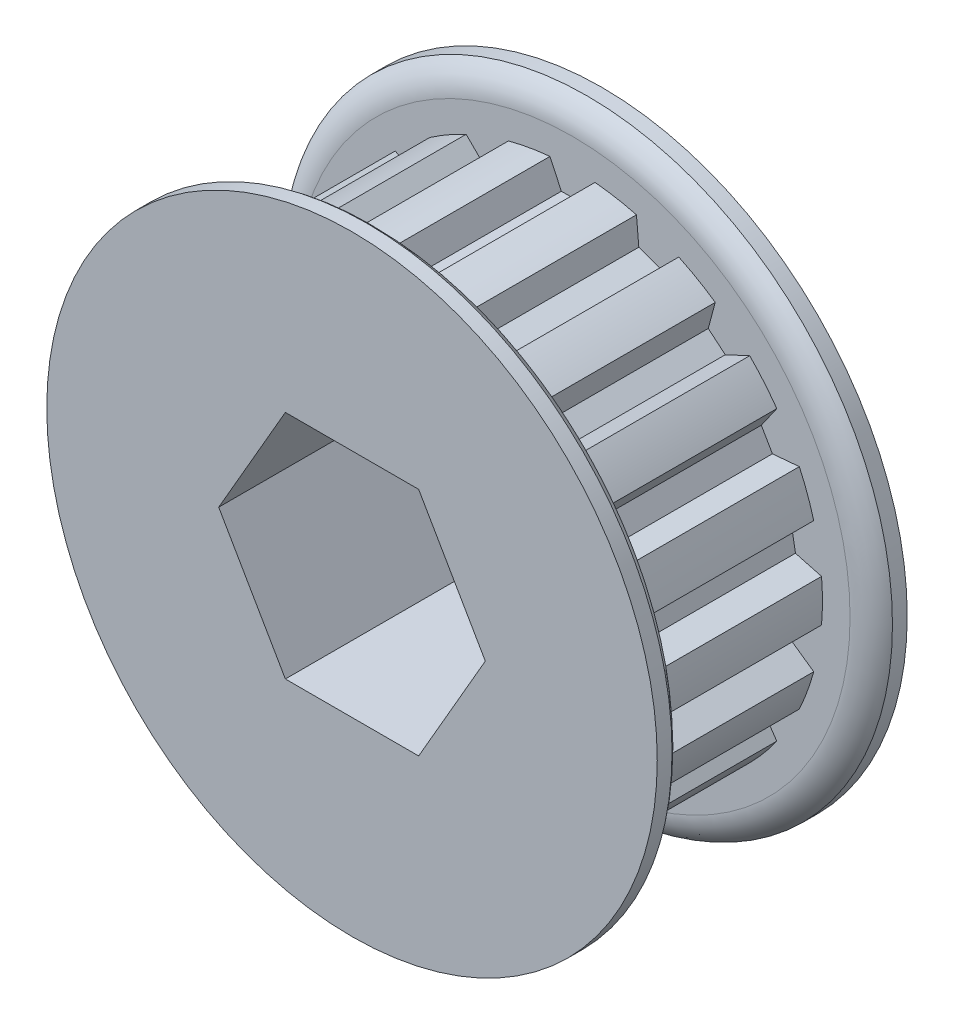
SolidWorks part; units mm, degrees
note: '?' marks a value the reader was unsure of.
ref_plane "Front Plane" through (0, 0, 0) normal (0, 0, 1) x (1, 0, 0)
ref_plane "Top Plane" through (0, 0, 0) normal (0, 1, 0) x (1, 0, 0)
ref_plane "Right Plane" through (0, 0, 0) normal (1, 0, 0) x (0, 0, -1)
sketch "Sketch1" plane through (0, 0, 0) normal (0, 0, 1) x (1, 0, 0)
  line L0 (-1.2878, 14.2421) -> (-0.635, 12.8421)
  line L1 (-0.635, 12.8421) -> (0.635, 12.8421)
  line L2 (0.635, 12.8421) -> (1.2878, 14.2421)
  line L3 (-1.2878, 14.2421) -> (1.2878, 14.2421)
  line L4 (0, 0) -> (0, 12.8421) construction
  line L5 (0, 12.8421) -> (0, 15.1281) construction
  circle A0 centre (0, 0) radius 14.5542 construction
  circle A1 centre (0, 0) radius 17.4625 construction
  circle A2 centre (0, 0) radius 14.3002 construction
  point P6 (0, 14.2421)
  point P11 (0, 14.5542)
  point P13 (0, 17.4625)
  point P14 (0, 14.3002)
  dimension "D1" = 1.4
  dimension "PD" = 29.1084
  dimension "OD" = 34.925
  dimension "D3" = 1.27
  dimension "Gear OD" = 28.6004
  dimension "b" = 50
  dimension "hs" = 2.286
sketch "Sketch2" plane through (0, 0, 0) normal (1, 0, 0) x (0, 0, -1)
  line L0 (-10.3124, 4.7625) -> (10.3124, 4.7625)
  line L1 (-10.3124, 4.7625) -> (-10.3124, 10.3124)
  line L2 (-10.3124, 10.3124) -> (-3.9878, 10.3124)
  line L3 (-3.9878, 10.3124) -> (-3.9878, 17.4625)
  line L4 (-3.9878, 17.4625) -> (-2.2987, 17.4625) construction
  line L5 (-2.2987, 17.4625) -> (-2.2987, 14.3002) construction
  line L6 (-2.2987, 14.3002) -> (8.6233, 14.3002)
  line L7 (8.6233, 14.3002) -> (8.6233, 17.4625) construction
  line L8 (8.6233, 17.4625) -> (10.3124, 17.4625) construction
  line L9 (10.3124, 17.4625) -> (10.3124, 4.7625)
  line L10 (-10.3124, 0) -> (10.3124, 0) construction
  line L13 (-3.9878, 17.4625) -> (-3.1432, 17.4625)
  line L14 (-2.2987, 15.8813) -> (-2.2987, 14.3002)
  line L15 (8.6233, 14.3002) -> (8.6233, 15.8813)
  line L16 (9.4679, 17.4625) -> (10.3124, 17.4625)
  arc A0 (-2.2987, 15.8813) -> (-3.1432, 17.4625) centre (-4.2011, 15.8813) ccw
  arc A1 (8.6233, 15.8813) -> (9.4679, 17.4625) centre (10.5257, 15.8813) cw
  point P12 (-2.2987, 15.8813)
  point P14 (-3.1432, 17.4625)
  point P20 (8.6233, 15.8813)
  point P21 (9.4679, 17.4625)
  point P25 (8.6233, 0)
  point P26 (-2.2987, 0)
  dimension "OA" = 20.6248
  dimension "Bore" = 9.525
  dimension "Hub Dia" = 20.6248
  dimension "Outside Width" = 14.3002
  dimension "Inside Width" = 10.922
revolve "Revolve1" add sketch "Sketch2" angle 360 mid plane about L10
sketch "Sketch3" plane through (0, 0, 0) normal (0, 0, 1) x (1, 0, 0)
  line L0 (-0.635, 12.8421) -> (0.635, 12.8421) construction
  line L1 (0.635, 12.8421) -> (1.2878, 14.2421) construction
  line L2 (-1.2878, 14.2421) -> (-0.635, 12.8421) construction
  line L3 (-0.635, 12.8421) -> (0.635, 12.8421)
  line L4 (0.635, 12.8421) -> (1.2878, 14.2421)
  line L5 (-1.2878, 14.2421) -> (-0.635, 12.8421)
  circle A0 centre (0, 0) radius 14.3002 construction
  arc A1 (1.2878, 14.2421) -> (-1.2878, 14.2421) centre (0, 0) ccw
extrude "Cut-Extrude1" cut sketch "Sketch3" against normal up to vertex (8.6233 mm away) from vertex at 2.2987 starting at point (0, 14.3002, 2.2987)
fillet "Fillet1" [suppressed] radius 0.61
pattern_circular "CirPattern1" count 18 over 360 about axis through (0, 0, 0) along (0, 0, 1) of "Cut-Extrude1", "Fillet1"
sketch "Sketch4" plane through (0, 0, 0) normal (0, 1, 0) x (1, 0, 0)
  line L0 (0, -3.9878) -> (0, -10.3124) construction
  circle A0 centre (0, -7.1501) radius 2.0828
  dimension "D1" = 4.1656
extrude "Cut-Extrude2" cut sketch "Sketch4" along normal through all
ref_plane "Plane1" through (0, 0, 7.1501) normal (0, 0, 1) x (1, 0, 0)
sketch "Sketch5" plane through (0, 0, 7.1501) normal (0, 0, 1) x (1, 0, 0)
  line L0 (0, 0) -> (0, 10.3124) construction
  line L1 (1.5748, 10.0999) -> (2.0828, 9.5919)
  line L2 (0, 10.0999) -> (1.5748, 10.0999)
  line L3 (0, 10.0999) -> (0, 4.7625)
  line L4 (0, 4.7625) -> (1.4478, 4.7625)
  line L5 (2.0828, 9.5919) -> (2.0828, 5.3975)
  line L6 (1.4478, 4.7625) -> (2.0828, 5.3975)
  circle A0 centre (0, 0) radius 10.3124 construction
  circle A1 centre (0, 0) radius 4.7625 construction
  point P7 (2.0828, 4.7625)
  point P9 (2.0828, 10.0999)
revolve "Revolve2" add sketch "Sketch5" angle 360 mid plane about L0
sketch "Sketch6" plane through (0, 10.0999, 0) normal (0, 1, 0) x (1, 0, 0)
  line L1 (0, -5.9476) -> (-1.0414, -6.5488)
  line L2 (-1.0414, -6.5488) -> (-1.0414, -7.7514)
  line L3 (-1.0414, -7.7514) -> (0, -8.3526)
  line L4 (0, -8.3526) -> (1.0414, -7.7514)
  line L5 (1.0414, -7.7514) -> (1.0414, -6.5488)
  line L6 (1.0414, -6.5488) -> (0, -5.9476)
  circle A0 centre (0, -7.1501) radius 1.0414 construction
  dimension "D1" = 2.0828
extrude "Cut-Extrude3" cut sketch "Sketch6" against normal blind 1.5621
pattern_circular "CirPattern2" count 2 every 90 about axis through (0, 0, 0) along (0, 0, 1) of "Cut-Extrude2", "Revolve2", "Cut-Extrude3"
ref_plane "Contact Plane 1" through (0, 0, 10.3124) normal (0, 0, 1) x (1, 0, 0)
ref_plane "Contact Plane 2" through (0, 0, -10.3124) normal (0, 0, -1) x (-1, 0, 0)
ref_axis "Center Axis 1" through (0, 0, -10.3124) along (0, 0, 1)?
sketch "Sketch7" plane through (0, 0, -10.3124) normal (0, 0, -1) x (-1, 0, 0)
  line L1 (3.8128, -6.604) -> (7.6256, 0)
  line L2 (7.6256, 0) -> (3.8128, 6.604)
  line L3 (3.8128, 6.604) -> (-3.8128, 6.604)
  line L4 (-3.8128, 6.604) -> (-7.6256, 0)
  line L5 (-7.6256, 0) -> (-3.8128, -6.604)
  line L6 (-3.8128, -6.604) -> (3.8128, -6.604)
  circle A0 centre (0, 0) radius 6.604 construction
  dimension "D1" = 13.208
extrude "Cut-Extrude4" cut sketch "Sketch7" against normal through all
sketch "Sketch8" plane through (0, 0, 3.9878) normal (0, 0, 1) x (1, 0, 0)
  circle A0 centre (0, 0) radius 13.8426
extrude "Cut-Extrude5" cut sketch "Sketch8" along normal through all
equation "\"D1@Sketch6\" = \"D1@Sketch4\"/2"
equation "\"D1@Cut-Extrude3\" = \"D1@Sketch6\"*.75"
